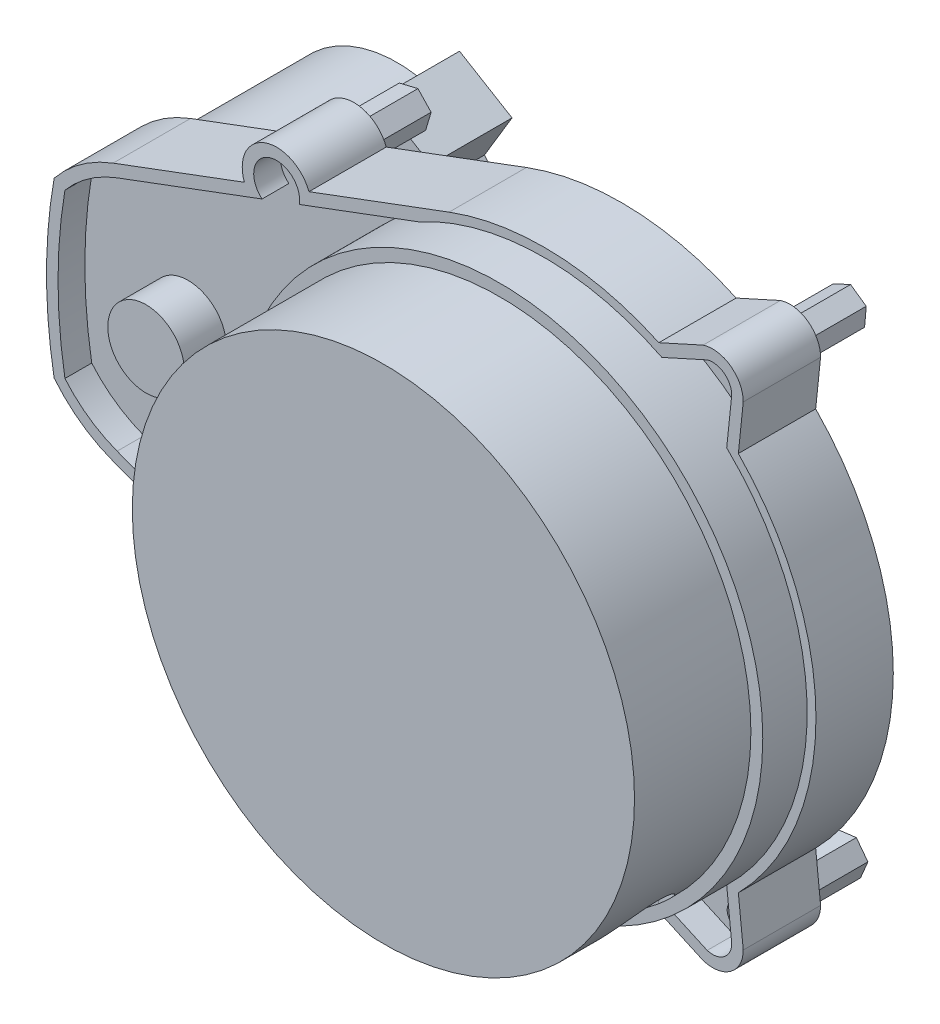
SolidWorks part; units mm, degrees
material "PET 90%"
ref_plane "Plan de face" through (0, 0, 0) normal (0, 0, 1) x (1, 0, 0)
ref_plane "Plan de dessus" through (0, 0, 0) normal (0, 1, 0) x (1, 0, 0)
ref_plane "Plan de droite" through (0, 0, 0) normal (1, 0, 0) x (0, 0, -1)
sketch "Esquisse1" plane through (0, 0, 0) normal (0, 0, 1) x (1, 0, 0)
  line L0 (-12.425, 33.2546) -> (-30.7256, 26.4169)
  line L1 (-56.3, 16.8615) -> (-56.3, -16.8615) construction
  line L2 (-50, 0) -> (0, 0) construction
  line L3 (-12.425, 33.2546) -> (-12.425, -33.2546) construction
  line L5 (-35, 25) -> (-34.9409, 24.8419) construction
  line L6 (-39.1563, 23.2669) -> (-56.3, 16.8615)
  line L7 (-33.4505, 25.3988) -> (-36.4314, 24.2851)
  line L8 (20.756, 34.8016) -> (14.974, 32.1874)
  line L9 (26, 31) -> (25.36, 24.8419)
  line L10 (-65, 0) -> (35.5, 0) construction
  line L11 (17.105, 0) -> (-17.105, 0) construction
  line L12 (-35, -25) -> (-34.9409, -24.8419) construction
  line L13 (26, -31) -> (25.36, -24.8419)
  line L14 (20.756, -34.8016) -> (14.974, -32.1874)
  line L15 (-33.4505, -25.3988) -> (-36.4314, -24.2851)
  line L16 (-39.1563, -23.2669) -> (-56.3, -16.8615)
  line L17 (-12.425, -33.2546) -> (-30.7256, -26.4169)
  arc A1 (25.36, -24.8419) -> (25.36, 24.8419) centre (0, 0) ccw
  arc A3 (-64.01, 11.3013) -> (-64.01, -11.3013) centre (0, 0) ccw
  arc A4 (-56.3, 16.8615) -> (-64.01, 11.3013) centre (-50, 0) ccw
  circle A5 centre (22, 31) radius 1.6
  circle A6 centre (-35, 25) radius 1.6
  arc A7 (-30.7256, 26.4169) -> (-39.1563, 23.2669) centre (-34.9409, 24.8419) ccw
  arc A8 (26, 31) -> (20.756, 34.8016) centre (22, 31) ccw
  arc A9 (14.974, 32.1874) -> (-12.425, 33.2546) centre (0, 0) ccw
  arc A10 (14.974, -32.1874) -> (-12.425, -33.2546) centre (0, 0) cw
  arc A11 (26, -31) -> (20.756, -34.8016) centre (22, -31) cw
  arc A12 (-30.7256, -26.4169) -> (-39.1563, -23.2669) centre (-34.9409, -24.8419) cw
  circle A13 centre (-35, -25) radius 1.6
  circle A14 centre (22, -31) radius 1.6
  arc A15 (-56.3, -16.8615) -> (-64.01, -11.3013) centre (-50, 0) cw
  point P28 (-12.425, 0)
  point P29 (-56.3, 0)
  dimension "D1" = 71
  dimension "D4" = 130
  dimension "D6" = 3.2
  dimension "D10" = 9
  dimension "D11" = 8
  dimension "D3" = 50
  dimension "D5" = 31
  dimension "D7" = 22
  dimension "D8" = 35
  dimension "D9" = 25
extrude "Boss.-Extru.1" add sketch "Esquisse1" along normal blind 10.1 contours A15 L16 A12 L17 A10 L14 A11 L13 A1 L9 A8 L8 A9 L0 A7 L6 A4 A3 A13 A5 A6 A14 region at (-11.042, 0, 0)
sketch "Esquisse2" plane through (0, 0, 10.1) normal (0, 0, 1) x (1, 0, 0)
  circle A0 centre (0, 0) radius 32.8
  dimension "D1" = 65.6
extrude "Boss.-Extru.2" add sketch "Esquisse2" along normal blind 21
sketch "Esquisse3" plane through (0, 0, 10.1) normal (0, 0, 1) x (1, 0, 0)
  line L16 (-55.775, -15.4564) -> (-36.8497, -22.5275)
  line L17 (14.9568, -30.5335) -> (21.2911, -33.3974)
  line L18 (24.4991, -31.0687) -> (23.7942, -24.2866)
  line L19 (23.7942, 24.2866) -> (24.4991, 31.0687)
  line L20 (21.2911, 33.3974) -> (14.9568, 30.5335)
  line L21 (-11.9, 31.8495) -> (-31.9822, 24.3461)
  line L22 (-55.775, -15.4564) -> (-36.8497, -22.5275)
  line L23 (14.9568, -30.5335) -> (21.2911, -33.3974)
  line L24 (24.4991, -31.0687) -> (23.7942, -24.2866)
  line L25 (23.7942, 24.2866) -> (24.4991, 31.0687)
  line L26 (21.2911, 33.3974) -> (14.9568, 30.5335)
  line L27 (-11.9, 31.8495) -> (-31.9822, 24.3461)
  line L28 (-31.9822, -24.3461) -> (-11.9, -31.8495)
  line L29 (-31.9822, -24.3461) -> (-11.9, -31.8495)
  line L30 (-36.8497, 22.5275) -> (-55.775, 15.4564)
  line L31 (-36.8497, 22.5275) -> (-55.775, 15.4564)
  arc A20 (-62.6, -10.6532) -> (-55.775, -15.4564) centre (-50, 0) ccw
  arc A21 (-11.9, -31.8495) -> (14.9568, -30.5335) centre (0, 0) ccw
  arc A22 (23.7942, -24.2866) -> (23.7942, 24.2866) centre (0, 0) ccw
  arc A23 (14.9568, 30.5335) -> (-11.9, 31.8495) centre (0, 0) ccw
  arc A24 (-55.775, 15.4564) -> (-62.6, 10.6532) centre (-50, 0) ccw
  arc A25 (-62.6, 10.6532) -> (-62.6, -10.6532) centre (0, 0) ccw
  arc A26 (-62.6, -10.6532) -> (-55.775, -15.4564) centre (-50, 0) ccw
  arc A27 (-11.9, -31.8495) -> (14.9568, -30.5335) centre (0, 0) ccw
  arc A28 (23.7942, -24.2866) -> (23.7942, 24.2866) centre (0, 0) ccw
  arc A29 (14.9568, 30.5335) -> (-11.9, 31.8495) centre (0, 0) ccw
  arc A30 (-55.775, 15.4564) -> (-62.6, 10.6532) centre (-50, 0) ccw
  arc A31 (-62.6, 10.6532) -> (-62.6, -10.6532) centre (0, 0) ccw
  arc A32 (-36.8497, -22.5275) -> (-31.9822, -24.3461) centre (-34.9409, -24.8419) ccw
  arc A33 (-36.8497, -22.5275) -> (-31.9822, -24.3461) centre (-34.9409, -24.8419) ccw
  arc A34 (21.2911, -33.3974) -> (24.4991, -31.0687) centre (22, -31) ccw
  arc A35 (21.2911, -33.3974) -> (24.4991, -31.0687) centre (22, -31) ccw
  arc A36 (24.4991, 31.0687) -> (21.2911, 33.3974) centre (22, 31) ccw
  arc A37 (24.4991, 31.0687) -> (21.2911, 33.3974) centre (22, 31) ccw
  arc A38 (-31.9822, 24.3461) -> (-36.8497, 22.5275) centre (-34.9409, 24.8419) ccw
  arc A39 (-31.9822, 24.3461) -> (-36.8497, 22.5275) centre (-34.9409, 24.8419) ccw
  dimension "D1" = 1.5
extrude "Enlèv. mat.-Extru.1" cut sketch "Esquisse3" against normal blind 3.5
sketch "Esquisse4" plane through (0, 0, 10.1) normal (0, 0, -1) x (-1, 0, 0)
  circle A1 centre (0, 0) radius 32.8
  circle A2 centre (0, 0) radius 32.8
  dimension "D1" = 0
extrude "Boss.-Extru.3" add sketch "Esquisse4" along normal up to next (3.5 mm away)
sketch "Esquisse5" plane through (0, 0, 0) normal (0, 0, -1) x (-1, 0, 0)
  circle A0 centre (50, 0) radius 16
  dimension "D2" = 32
  dimension "D1" = 50
extrude "Boss.-Extru.4" add sketch "Esquisse5" along normal blind 20.7
ref_plane "Plan1" through (0, 0, -7.7) normal (0, 0, -1) x (-1, 0, 0)
sketch "Esquisse8" plane through (0, 0, 6.6) normal (0, 0, 1) x (1, 0, 0)
  circle A0 centre (-50, 0) radius 5
  dimension "D1" = 10
extrude "Boss.-Extru.7" add sketch "Esquisse8" along normal blind 5.5
sketch "Sketch6" plane through (0, 0, 6.6) normal (0, 0, 1) x (1, 0, 0)
  circle A0 centre (0, 0) radius 34.35
  dimension "D1" = 68.7
extrude "Boss-Extrude3" add sketch "Sketch6" along normal offset from surface (9.3 mm away) 15.2 up to face at (32.8, 0, 31.1)
ref_axis "Laser spin" through (0, 0, 37.702) along (0, 0, 1)
ref_plane "Laser" through (0, 0, 21.7) normal (0, 0, 1) x (1, 0, 0)
ref_plane "Upper laser volume" through (0, 0, 26.95) normal (0, 0, 1) x (1, 0, 0)
ref_plane "Lower laser volume" through (0, 0, 16.45) normal (0, 0, 1) x (1, 0, 0)
sketch "Sketch1" plane through (0, 0, 16.45) normal (0, 0, 1) x (1, 0, 0)
  circle A0 centre (0, 0) radius 250
  dimension "D1" = 500
extrude "Boss-Extrude1" [suppressed] add sketch "Sketch1" along normal blind 10
ref_point "Laser source"
sketch "Sketch5" plane through (0, 0, 0) normal (0, 1, 0) x (1, 0, 0)
  line L0 (0, -21.7) -> (-18, -21.7) construction
  line L1 (0, -21.7) -> (18, -21.7) construction
  line L2 (14.75, -21.7) -> (21.25, -21.7) construction
  line L3 (14.75, -16.45) -> (21.25, -16.45)
  line L4 (14.75, -26.95) -> (21.25, -26.95)
  line L5 (21.25, -26.95) -> (-18, -26.95) construction
  circle A0 centre (-18, -21.7) radius 5.25
  arc A1 (14.75, -16.45) -> (14.75, -26.95) centre (14.75, -21.7) ccw
  arc A2 (21.25, -26.95) -> (21.25, -16.45) centre (21.25, -21.7) ccw
  point P7 (18, -21.7)
  point P14 (9.5, -21.7)
  point P15 (26.5, -21.7)
  point P16 (0, 0)
  point P17 (46.7981, -21.7)
  point P18 (0, 0)
  point P19 (-20.6096, -21.7)
  point P20 (16.9078, -21.7)
  dimension "D1" = 10.5
  dimension "D2" = 18
  dimension "D3" = 17
  dimension "D4" = 18
extrude "Cut-Extrude1" cut sketch "Sketch5" against normal up to next
sketch "Esquisse6" plane through (0, 0, 0) normal (0, 0, -1) x (-1, 0, 0)
  line L1 (-20.4892, -29.0081) -> (-22.9696, -28.6957)
  line L2 (-22.9696, -28.6957) -> (-24.4804, -30.6876)
  line L3 (-24.4804, -30.6876) -> (-23.5108, -32.9919)
  line L4 (-23.5108, -32.9919) -> (-21.0304, -33.3043)
  line L5 (-21.0304, -33.3043) -> (-19.5196, -31.3124)
  line L6 (-19.5196, -31.3124) -> (-20.4892, -29.0081)
  line L7 (36.0868, -22.7486) -> (33.5937, -22.9331)
  line L8 (33.5937, -22.9331) -> (32.5068, -25.1845)
  line L9 (32.5068, -25.1845) -> (33.9132, -27.2514)
  line L10 (33.9132, -27.2514) -> (36.4063, -27.0669)
  line L11 (36.4063, -27.0669) -> (37.4932, -24.8155)
  line L12 (37.4932, -24.8155) -> (36.0868, -22.7486)
  line L13 (36.7203, 26.814) -> (34.2892, 27.3968)
  line L14 (34.2892, 27.3968) -> (32.5689, 25.5828)
  line L15 (32.5689, 25.5828) -> (33.2797, 23.186)
  line L16 (33.2797, 23.186) -> (35.7108, 22.6032)
  line L17 (35.7108, 22.6032) -> (37.4311, 24.4172)
  line L18 (37.4311, 24.4172) -> (36.7203, 26.814)
  line L19 (-19.9522, 32.434) -> (-22.218, 33.4905)
  line L20 (-22.218, 33.4905) -> (-24.2658, 32.0565)
  line L21 (-24.2658, 32.0565) -> (-24.0478, 29.566)
  line L22 (-24.0478, 29.566) -> (-21.782, 28.5095)
  line L23 (-21.782, 28.5095) -> (-19.7342, 29.9435)
  line L24 (-19.7342, 29.9435) -> (-19.9522, 32.434)
  circle A0 centre (-22, -31) radius 2.1651 construction
  circle A1 centre (35, -25) radius 2.1651 construction
  circle A2 centre (35, 25) radius 2.1651 construction
  circle A3 centre (-22, 31) radius 2.1651 construction
  circle A4 centre (35, -25) radius 1
  circle A5 centre (35, 25) radius 1
  circle A6 centre (-22, 31) radius 1
  circle A7 centre (-22, -31) radius 1
  dimension "D2" = 2
  dimension "D1" = 5
extrude "Boss.-Extru.5" add sketch "Esquisse6" along normal up to surface (7.7 mm away) up to plane "Plan1"
sketch "Esquisse7" plane through (0, 0, -7.7) normal (0, 0, -1) x (-1, 0, 0)
  line L0 (50, 0) -> (80, 0) construction
  line L8 (56.3, 16.8615) -> (39.1563, 23.2669)
  line L9 (30.7256, 26.4169) -> (12.425, 33.2546)
  line L10 (-14.974, 32.1874) -> (-20.756, 34.8016)
  line L11 (-26, 31) -> (-25.36, 24.8419)
  line L12 (-25.36, -24.8419) -> (-26, -31)
  line L13 (-20.756, -34.8016) -> (-14.974, -32.1874)
  line L14 (12.425, -33.2546) -> (30.7256, -26.4169)
  line L15 (39.1563, -23.2669) -> (56.3, -16.8615)
  line L17 (30.7256, 26.4169) -> (12.425, 33.2546)
  line L18 (-14.974, 32.1874) -> (-20.756, 34.8016)
  line L19 (-26, 31) -> (-25.36, 24.8419)
  line L20 (-25.36, -24.8419) -> (-26, -31)
  line L21 (-20.756, -34.8016) -> (-14.974, -32.1874)
  line L22 (12.425, -33.2546) -> (30.7256, -26.4169)
  arc A0 (39.1563, 23.2669) -> (39.1563, -23.2669) centre (80, 0) ccw
  arc A12 (64.69, 6.3407) -> (64.69, -6.3407) centre (50, 0) ccw
  arc A13 (64.69, 6.3407) -> (64.01, 11.3013) centre (0, 0) ccw
  arc A14 (64.01, 11.3013) -> (56.3, 16.8615) centre (50, 0) ccw
  arc A15 (39.1563, 23.2669) -> (30.7256, 26.4169) centre (34.9409, 24.8419) ccw
  arc A16 (12.425, 33.2546) -> (-14.974, 32.1874) centre (0, 0) ccw
  arc A17 (-20.756, 34.8016) -> (-26, 31) centre (-22, 31) ccw
  arc A18 (-25.36, 24.8419) -> (-25.36, -24.8419) centre (0, 0) ccw
  arc A19 (-26, -31) -> (-20.756, -34.8016) centre (-22, -31) ccw
  arc A20 (-14.974, -32.1874) -> (12.425, -33.2546) centre (0, 0) ccw
  arc A21 (30.7256, -26.4169) -> (39.1563, -23.2669) centre (34.9409, -24.8419) ccw
  arc A22 (56.3, -16.8615) -> (64.01, -11.3013) centre (50, 0) ccw
  arc A23 (64.01, -11.3013) -> (64.69, -6.3407) centre (0, 0) ccw
  arc A27 (39.1563, 23.2669) -> (30.7256, 26.4169) centre (34.9409, 24.8419) ccw
  arc A28 (12.425, 33.2546) -> (-14.974, 32.1874) centre (0, 0) ccw
  arc A29 (-20.756, 34.8016) -> (-26, 31) centre (-22, 31) ccw
  arc A30 (-25.36, 24.8419) -> (-25.36, -24.8419) centre (0, 0) ccw
  arc A31 (-26, -31) -> (-20.756, -34.8016) centre (-22, -31) ccw
  arc A32 (-14.974, -32.1874) -> (12.425, -33.2546) centre (0, 0) ccw
  arc A33 (30.7256, -26.4169) -> (39.1563, -23.2669) centre (34.9409, -24.8419) ccw
  dimension "D2" = 30
  dimension "D1" = 0
extrude "Optional plate" [suppressed] add sketch "Esquisse7" along normal blind 2
sketch "Sketch4" [suppressed] plane through (0, 0, -9.7) normal (0, 0, -1) x (-1, 0, 0)
  line L6 (-20.4892, -29.0081) -> (-22.9696, -28.6957)
  line L7 (-22.9696, -28.6957) -> (-24.4804, -30.6876)
  line L8 (-24.4804, -30.6876) -> (-23.5108, -32.9919)
  line L9 (-23.5108, -32.9919) -> (-21.0304, -33.3043)
  line L10 (-21.0304, -33.3043) -> (-19.5196, -31.3124)
  line L11 (-19.5196, -31.3124) -> (-20.4892, -29.0081)
  line L12 (-20.4892, -29.0081) -> (-22.9696, -28.6957)
  line L13 (-22.9696, -28.6957) -> (-24.4804, -30.6876)
  line L14 (-24.4804, -30.6876) -> (-23.5108, -32.9919)
  line L15 (-23.5108, -32.9919) -> (-21.0304, -33.3043)
  line L16 (-21.0304, -33.3043) -> (-19.5196, -31.3124)
  line L17 (-19.5196, -31.3124) -> (-20.4892, -29.0081)
  line L18 (36.7203, 26.814) -> (34.2892, 27.3968)
  line L19 (34.2892, 27.3968) -> (32.5689, 25.5828)
  line L20 (32.5689, 25.5828) -> (33.2797, 23.186)
  line L21 (33.2797, 23.186) -> (35.7108, 22.6032)
  line L22 (35.7108, 22.6032) -> (37.4311, 24.4172)
  line L23 (37.4311, 24.4172) -> (36.7203, 26.814)
  line L24 (36.7203, 26.814) -> (34.2892, 27.3968)
  line L25 (34.2892, 27.3968) -> (32.5689, 25.5828)
  line L26 (32.5689, 25.5828) -> (33.2797, 23.186)
  line L27 (33.2797, 23.186) -> (35.7108, 22.6032)
  line L28 (35.7108, 22.6032) -> (37.4311, 24.4172)
  line L29 (37.4311, 24.4172) -> (36.7203, 26.814)
  line L30 (36.4063, -27.0669) -> (37.4932, -24.8155)
  line L31 (33.9132, -27.2514) -> (36.4063, -27.0669)
  line L32 (32.5068, -25.1845) -> (33.9132, -27.2514)
  line L33 (33.5937, -22.9331) -> (32.5068, -25.1845)
  line L34 (36.0868, -22.7486) -> (33.5937, -22.9331)
  line L35 (37.4932, -24.8155) -> (36.0868, -22.7486)
  line L36 (36.4063, -27.0669) -> (37.4932, -24.8155)
  line L37 (33.9132, -27.2514) -> (36.4063, -27.0669)
  line L38 (32.5068, -25.1845) -> (33.9132, -27.2514)
  line L39 (33.5937, -22.9331) -> (32.5068, -25.1845)
  line L40 (36.0868, -22.7486) -> (33.5937, -22.9331)
  line L41 (37.4932, -24.8155) -> (36.0868, -22.7486)
  line L42 (-24.0478, 29.566) -> (-21.782, 28.5095)
  line L43 (-21.782, 28.5095) -> (-19.7342, 29.9435)
  line L44 (-19.7342, 29.9435) -> (-19.9522, 32.434)
  line L45 (-19.9522, 32.434) -> (-22.218, 33.4905)
  line L46 (-22.218, 33.4905) -> (-24.2658, 32.0565)
  line L47 (-24.2658, 32.0565) -> (-24.0478, 29.566)
  line L48 (-24.0478, 29.566) -> (-21.782, 28.5095)
  line L49 (-21.782, 28.5095) -> (-19.7342, 29.9435)
  line L50 (-19.7342, 29.9435) -> (-19.9522, 32.434)
  line L51 (-19.9522, 32.434) -> (-22.218, 33.4905)
  line L52 (-22.218, 33.4905) -> (-24.2658, 32.0565)
  line L53 (-24.2658, 32.0565) -> (-24.0478, 29.566)
  circle A1 centre (35, -25) radius 1
  circle A2 centre (35, -25) radius 1
  circle A3 centre (-22, -31) radius 1
  circle A4 centre (-22, -31) radius 1
  circle A5 centre (-22, 31) radius 1
  circle A6 centre (-22, 31) radius 1
  circle A7 centre (35, 25) radius 1
  circle A8 centre (35, 25) radius 1
  dimension "D1" = 0
  dimension "D2" = 0
  dimension "D3" = 0
  dimension "D4" = 0
  dimension "D5" = 0
  dimension "D6" = 0
  dimension "D7" = 0
  dimension "D8" = 0
extrude "Optional standoffs" [suppressed] add sketch "Sketch4" along normal blind 18
sketch "Sketch7" plane through (0, 0, -20.7) normal (0, 0, -1) x (-1, 0, 0)
  line L0 (35, 25) -> (50, 0) construction
  line L1 (45.4594, 15.3422) -> (41.858, 21.3447)
  line L2 (41.858, 21.3447) -> (38.428, 19.2867)
  line L3 (38.428, 19.2867) -> (34.998, 17.2287)
  line L4 (34.998, 17.2287) -> (38.5995, 11.2262)
  circle A0 centre (50, 0) radius 16 construction
  arc A1 (45.4594, 15.3422) -> (38.5995, 11.2262) centre (50, 0) ccw
  dimension "D1" = 7
  dimension "D2" = 8
extrude "Boss-Extrude4" add sketch "Sketch7" against normal blind 10.6
